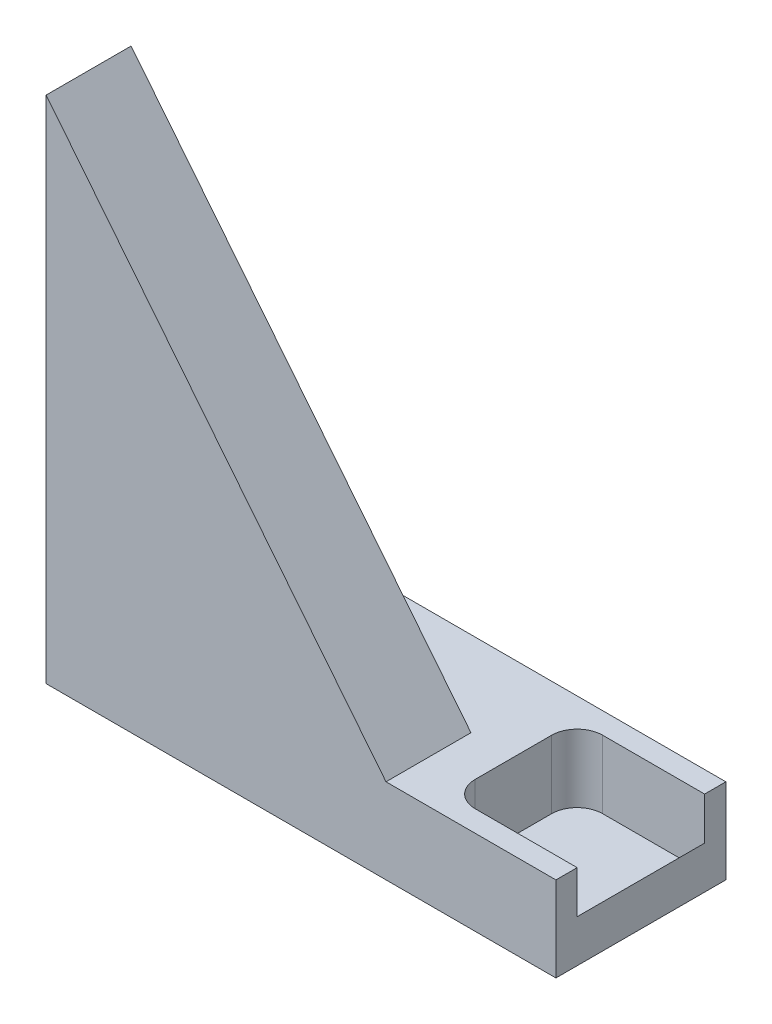
SolidWorks part; units mm, degrees
ref_plane "Ebene vorne" through (0, 0, 0) normal (0, 0, 1) x (1, 0, 0)
ref_plane "Ebene oben" through (0, 0, 0) normal (0, 1, 0) x (1, 0, 0)
ref_plane "Ebene rechts" through (0, 0, 0) normal (1, 0, 0) x (0, 0, -1)
sketch "Skizze1" plane through (0, 0, 0) normal (0, 0, 1) x (1, 0, 0)
  line L1 (40, 10) -> (0, 60)
  line L2 (0, 60) -> (0, 0)
  line L4 (0, 0) -> (60, 0)
  line L5 (60, 0) -> (60, 10)
  line L6 (60, 10) -> (40, 10)
  point P6 (0, -16.4528)
  point P8 (0, 0)
  point P9 (0, -15.6899)
  dimension "D1" = 20
  dimension "D2" = 60
  dimension "D3" = 60
  dimension "D4" = 10
extrude "Aufsatz-Linear austragen1" add sketch "Skizze1" along normal blind 10
sketch "Skizze2" plane through (0, 0, 0) normal (0, 0, -1) x (-1, 0, 0)
  line L0 (0, 60) -> (0, 0) construction
  line L1 (-60, 0) -> (0, 0)
  line L2 (-60, 0) -> (-60, 10)
  line L3 (-60, 10) -> (0, 10)
  line L4 (0, 0) -> (0, 10)
  line L5 (-60, 0) -> (-60, 10) construction
  point P7 (-60, 10)
extrude "Aufsatz-Linear austragen2" add sketch "Skizze2" along normal blind 10
sketch "Skizze4" plane through (0, 0, 0) normal (0, 0, 1) x (1, 0, 0)
  line L0 (60, 10) -> (45, 10)
  line L1 (0, 10) -> (60, 10) construction
  line L2 (60, 10) -> (60, 0) construction
  line L3 (45, 10) -> (45, 2)
  line L4 (45, 2) -> (58, 2)
  line L5 (58, 2) -> (58, 5)
  line L6 (58, 5) -> (60, 5)
  line L7 (60, 5) -> (60, 10)
  dimension "D1" = 8
  dimension "D2" = 15
  dimension "D3" = 2
extrude "Schnitt-Linear austragen2" cut sketch "Skizze4" against normal blind 7.5 and the other way blind 7.5
chamfer "Fase1" distance 2 angle 45 1 edges at (58, 5, 0)
fillet "Verrundung1" radius 3 2 edges at (45, 6, -7.5) (45, 6, 7.5)
